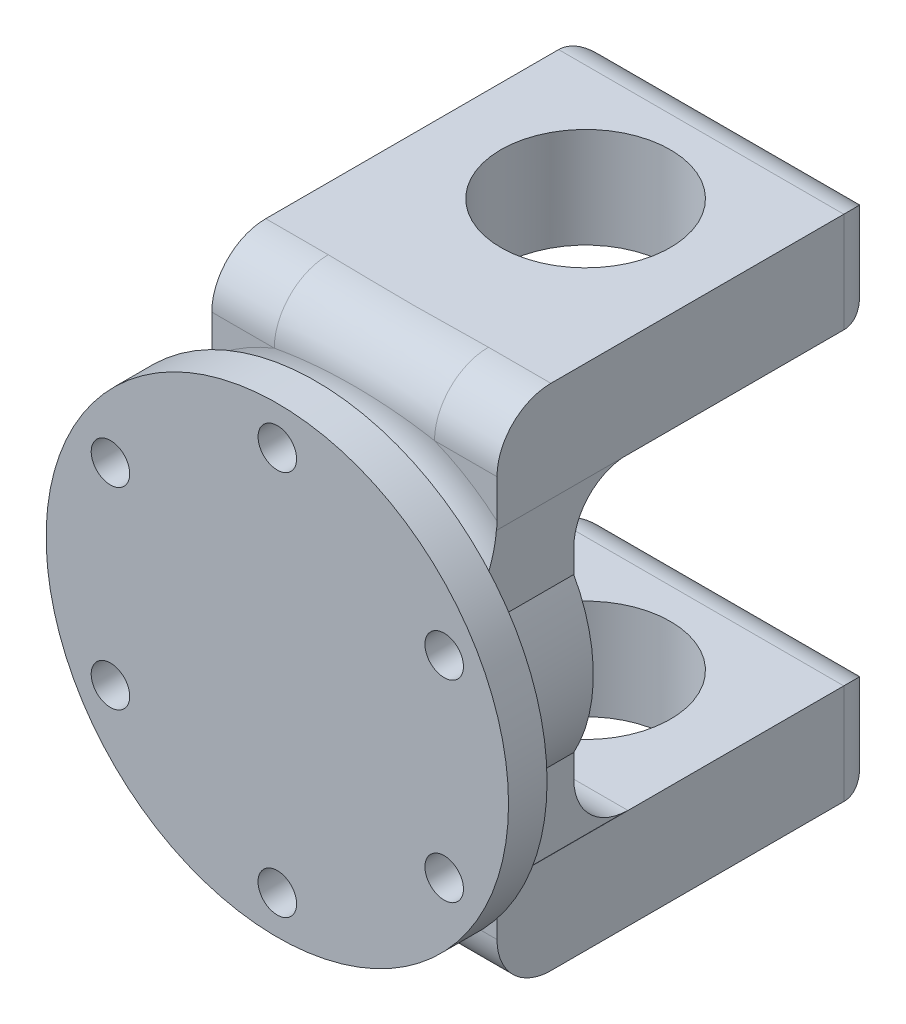
SolidWorks part; units mm, degrees
ref_plane "Płaszczyzna przednia" through (0, 0, 0) normal (0, 0, 1) x (1, 0, 0)
ref_plane "Płaszczyzna górna" through (0, 0, 0) normal (0, 1, 0) x (1, 0, 0)
ref_plane "Płaszczyzna prawa" through (0, 0, 0) normal (1, 0, 0) x (0, 0, -1)
sketch "Szkic1" plane through (0, 0, 0) normal (0, 0, 1) x (1, 0, 0)
  circle A1 centre (0, 0) radius 21
  dimension "D2" = 42
extrude "Dodanie-wyciągnięcie1" add sketch "Szkic1" along normal blind 15 contours A1 region at (0, 0, 0)
ref_plane "Płaszczyzna1" through (0, 0, -40) normal (0, 0, -1) x (-1, 0, 0)
sketch "Szkic6" plane through (0, 0, 15) normal (0, 0, 1) x (1, 0, 0)
  circle A0 centre (0, 0) radius 30
  dimension "D1" = 60
extrude "Dodanie-wyciągnięcie3" add sketch "Szkic6" along normal blind 5
sketch "Szkic7" plane through (0, 0, 20) normal (0, 0, 1) x (1, 0, 0)
  circle A0 centre (0, 25) radius 2.5
  dimension "D1" = 5
  dimension "D2" = 25
extrude "Wytnij-wyciągnięcie2" cut sketch "Szkic7" against normal blind 5
pattern_circular "Szyk kołowy1" count 6 over 360 about axis through (0, 0, 20) along (0, 0, 1) of "Wytnij-wyciągnięcie2"
sketch "Szkic8" plane through (0, 0, -40) normal (0, 0, -1) x (-1, 0, 0)
  line L1 (-18.5, 33) -> (18.5, 33)
  line L2 (-18.5, 33) -> (-18.5, 20)
  line L3 (-18.5, 20) -> (18.5, 20)
  line L4 (18.5, 33) -> (18.5, 20)
  point P4 (0, 20)
  dimension "D1" = 37
  dimension "D2" = 13
  dimension "D3" = 33
ref_plane "Płaszczyzna2" through (0, 10, 0) normal (0, 1, 0) x (1, 0, 0)
sketch "Szkic9" plane through (0, 10, 0) normal (0, 1, 0) x (1, 0, 0)
  line L1 (-18.4662, 0) -> (18.4662, 0)
  line L2 (-18.4662, 0) -> (-18.4662, -10)
  line L3 (-18.4662, -10) -> (18.4662, -10)
  line L4 (18.4662, 0) -> (18.4662, -10)
  dimension "D1" = 10
extrude "Dodanie-wyciągnięcie4" add sketch "Szkic8" against normal blind 50 contours L1 L4 L3 L2
extrude "Dodanie-wyciągnięcie5" add sketch "Szkic9" along normal up to next (23 mm away) contours L4 L3 L2 L1
fillet "Zaokrąglenie1" radius 7 2 edges at (0, 20, 0) (0, 21, 10)
fillet "Zaokrąglenie2" radius 7 1 edges at (0, 33, 10)
mirror "Lustro1" about plane through (0, 0, 0) normal (0, 1, 0) of "Dodanie-wyciągnięcie5", "Zaokrąglenie1", "Zaokrąglenie2", "Dodanie-wyciągnięcie4"
sketch "Szkic10" plane through (0, 33, 0) normal (0, 1, 0) x (1, 0, 0)
  line L0 (18.5, 40) -> (-18.5, 40) construction
  circle A0 centre (0, 20) radius 11
  dimension "D1" = 22
  dimension "D2" = 20
extrude "Wytnij-wyciągnięcie3" cut sketch "Szkic10" against normal through all
fillet "Zaokrąglenie3" radius 5 8 edges at (0, -20, -40) (-18.5, -26.5, -40) (0, -33, -40) (18.5, -26.5, -40) (0, 33, -40) (-18.5, 26.5, -40) (0, 20, -40) (18.5, 26.5, -40)
